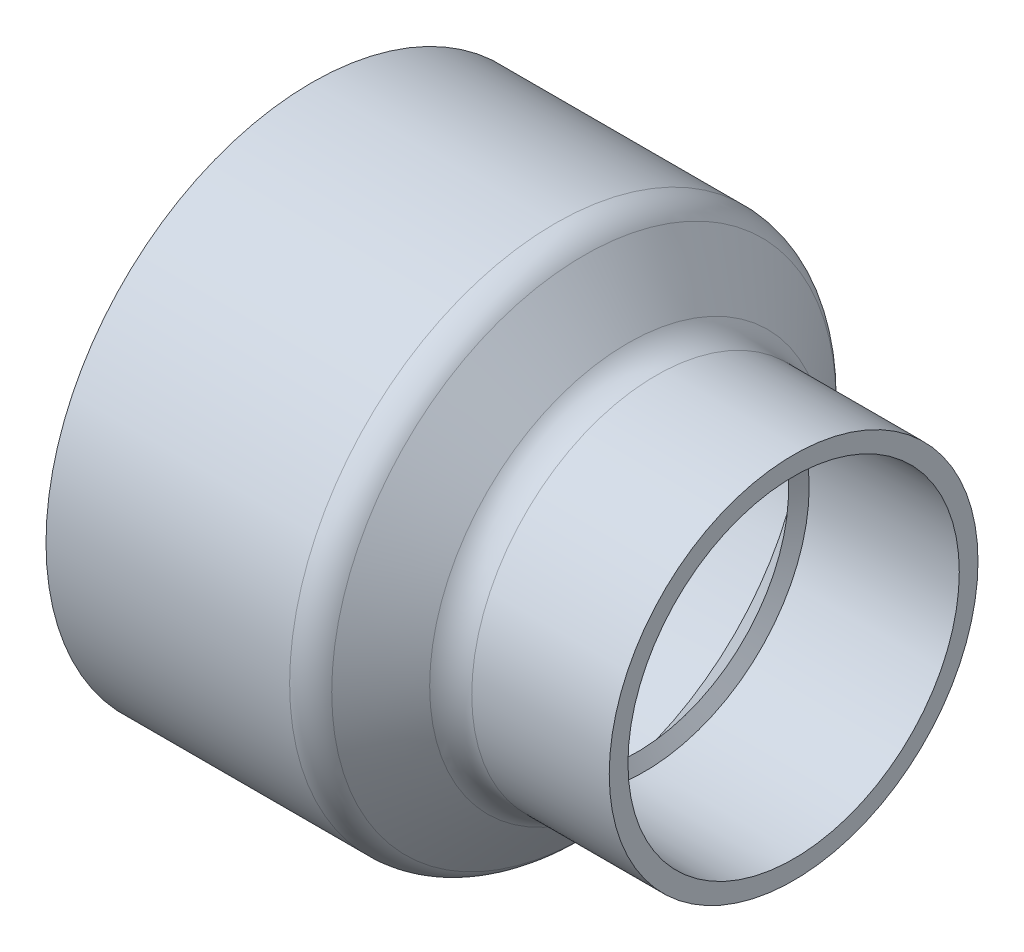
SolidWorks part; units mm, degrees
ref_plane "Front Plane" through (0, 0, 0) normal (0, 0, 1) x (1, 0, 0)
ref_plane "Top Plane" through (0, 0, 0) normal (0, 1, 0) x (1, 0, 0)
ref_plane "Right Plane" through (0, 0, 0) normal (1, 0, 0) x (0, 0, -1)
sketch "Sketch0" plane through (0, 0, 0) normal (0, 0, 1) x (1, 0, 0)
  line L0 (-83.4517, 0) -> (31.8135, 0) construction
  line L2 (3.6957, 0) -> (31.8135, 0) construction
  line L3 (-83.4517, 0) -> (83.4517, 0) construction
  line L4 (-83.4517, 92.0115) -> (-83.4517, -92.0115) construction
  line L5 (3.6957, 83.9978) -> (-83.4517, 84.4169) construction
  line L6 (3.6957, 83.9978) -> (3.6957, -83.9978) construction
  line L7 (3.6957, -83.9978) -> (-83.4517, -84.4169) construction
  line L8 (-83.4517, 84.4169) -> (-83.4517, -84.4169) construction
  line L9 (83.4517, 57.3786) -> (83.4517, -57.3786) construction
  line L10 (83.4517, 63.8556) -> (83.4517, -63.8556) construction
  line L11 (31.8135, 51.1302) -> (31.8135, -51.1302) construction
  line L12 (31.8135, 57.0357) -> (31.8135, -57.0357) construction
  line L13 (31.8135, -57.0357) -> (83.4517, -57.3786) construction
  line L14 (3.6957, 77.0255) -> (3.6957, -77.0255) construction
  line L15 (31.8135, 57.0357) -> (83.4517, 57.3786) construction
  dimension "N" = 28.1178
  dimension "M" = 184.023
  dimension "OD A" = 168.8338
  dimension "OD B" = 167.9956
  dimension "ID" = 154.051
  dimension "L" = 166.9034
  dimension "ID2" = 102.2604
  dimension "OD B2" = 114.0714
  dimension "OD A2" = 114.7572
  dimension "M2" = 127.7112
  dimension "C" = 87.1474
  dimension "C2" = 51.6382
sketch "Sketch1" plane through (0, 0, 0) normal (0, 0, 1) x (1, 0, 0)
  line L0 (-83.4517, 0) -> (31.8135, 0) construction
  line L1 (-83.4517, 0) -> (31.8135, 0) construction
  line L2 (3.6957, -83.9978) -> (29.1979, -52.5053)
  line L3 (0, -100.6295) -> (-5.9021, -95.8501) construction
  line L4 (-83.4517, -92.0115) -> (-83.4517, -84.4169)
  line L5 (-83.4517, -84.4169) -> (3.6957, -83.9978)
  line L7 (29.1979, -52.5053) -> (31.8135, -57.0357)
  line L8 (6.9788, -92.0115) -> (29.779, -63.8556)
  line L9 (6.9788, -92.0115) -> (-83.4517, -92.0115)
  line L10 (0, 0) -> (0, -100.6295) construction
  line L12 (31.8135, -57.0357) -> (83.4517, -57.3786)
  line L13 (83.4517, -57.3786) -> (83.4517, -63.8556)
  line L14 (83.4517, -63.8556) -> (29.779, -63.8556)
  dimension "D1" = 39
  dimension "D2" = 30
revolve "Revolve1" add sketch "Sketch1" angle 360 about L1
fillet "Fillet1" radius 12.7 2 edges at (6.9788, 0, 92.0115) (29.779, 0, 63.8556)
other "CPoint1" parameters "Diameter"=101.6, "StubLength"=228.6
ref_axis "Axis1" through (39.1979, 0, 0) along (-1, 0, 0)
other "CPoint2" parameters "Diameter"=152.4, "StubLength"=152.4
ref_axis "Axis2" through (-6.3043, 0, 0) along (1, 0, 0)
other "RPoint1"
